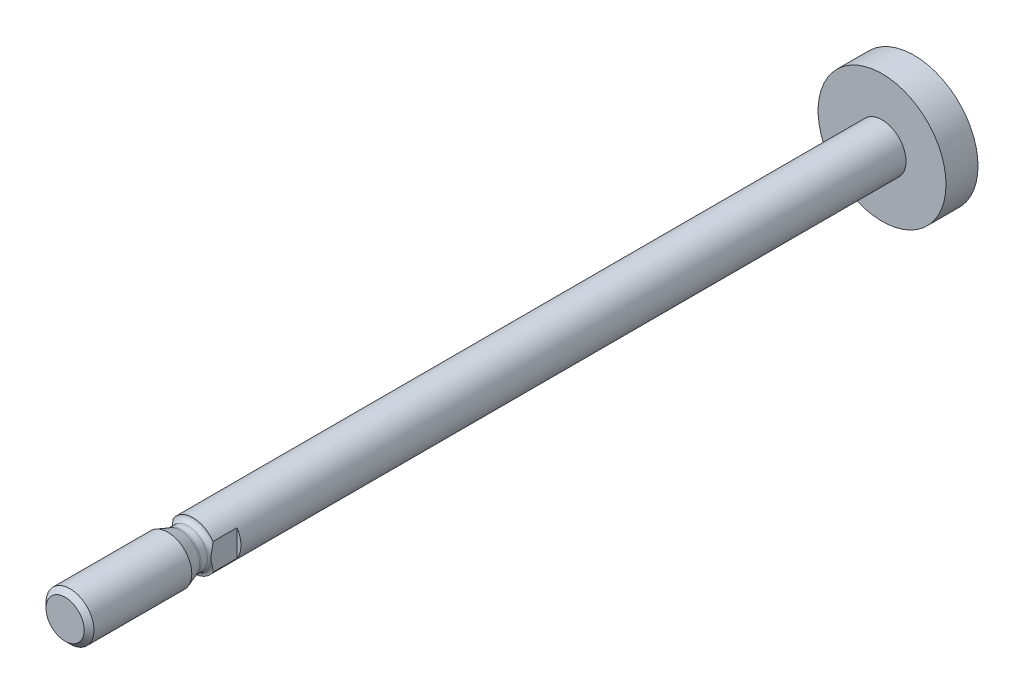
SolidWorks part; units mm, degrees
ref_plane "Front Plane" through (0, 0, 0) normal (0, 0, 1) x (1, 0, 0)
ref_plane "Top Plane" through (0, 0, 0) normal (0, 1, 0) x (1, 0, 0)
ref_plane "Right Plane" through (0, 0, 0) normal (1, 0, 0) x (0, 0, -1)
sketch "Sketch1" plane through (0, 0, 0) normal (1, 0, 0) x (0, 0, -1)
  line L0 (-5, 0) -> (-5, 3)
  line L1 (-5, 3) -> (81.2, 3)
  line L2 (81.2, 3) -> (81.2, 8)
  line L3 (81.2, 8) -> (85.2, 8)
  line L4 (85.2, 8) -> (85.2, 0)
  line L5 (85.2, 0) -> (-5, 0)
  line L6 (85.2, 0) -> (-5, 0) construction
revolve "Revolve1" add sketch "Sketch1" angle 360 about L6 reverse direction yes
sketch "Sketch2" plane through (0, 0, 0) normal (1, 0, 0) x (0, 0, -1)
  line L0 (-21, 0) -> (-21, 2.3865)
  line L1 (-21, 2.3865) -> (-20.3865, 3)
  line L2 (-20.3865, 3) -> (-8.1485, 3)
  line L3 (-8.1485, 3) -> (-6.5994, 2.4362)
  line L4 (-6.3942, 2.4) -> (-5.6, 2.4)
  line L5 (-5, 3) -> (-4, 3)
  line L6 (-4, 3) -> (-4, 0)
  line L7 (-4, 0) -> (-21, 0)
  line L8 (-4, 0) -> (-21, 0) construction
  arc A0 (-6.5994, 2.4362) -> (-6.3942, 2.4) centre (-6.3942, 3) ccw
  arc A1 (-5.6, 2.4) -> (-5, 3) centre (-5.6, 3) ccw
revolve "Revolve2" add sketch "Sketch2" angle 360 about L8 reverse direction yes
cosmetic thread "Cosmetic Thread1" parameters "D1"=12.8515, "D2"=4.773
ref_plane "Plane1" through (0, 0, 5) normal (0, 0, 1) x (1, 0, 0)
ref_plane "Plane2" through (0, 0, 2) normal (0, 0, 1) x (1, 0, 0)
sketch "Sketch3" plane through (0, 0, 2) normal (0, 0, 1) x (1, 0, 0)
  line L0 (-5, 10) -> (-5, -5)
  line L1 (-5, -5) -> (-2.5, -5)
  line L2 (-2.5, -5) -> (-2.5, 5)
  line L3 (-2.5, 5) -> (2.5, 5)
  line L4 (2.5, 5) -> (2.5, -5)
  line L5 (2.5, -5) -> (5, -5)
  line L6 (5, -5) -> (5, 10)
  line L7 (5, 10) -> (-5, 10)
extrude "Cut-Extrude1" cut sketch "Sketch3" along normal blind 4
ref_plane "Plane3" through (0, 0, -175) normal (0, 0, 1) x (1, 0, 0)
ref_plane "Plane4" through (0, 0, 16) normal (0, 0, 1) x (1, 0, 0)
ref_plane "Plane5" through (0, 0, 11.2) normal (0, 0, 1) x (1, 0, 0)
ref_plane "FDT_KSAUFSATZ XY" through (0, 0, 11.2) normal (0, 0, 1) x (1, 0, 0)
ref_plane "FDT_KSAUFSATZ XZ" through (0, 0, 0) normal (0, 1, 0) x (1, 0, 0)
ref_plane "FDT_KSAUFSATZ YZ" through (0, 0, 0) normal (-1, 0, 0) x (0, 0, 1)
ref_axis "FDT_KSAUFSATZ X" through (80.9, 0, 11.2) along (-1, 0, 0)
ref_axis "FDT_KSAUFSATZ Y" through (0, 50, 11.2) along (0, -1, 0)
ref_axis "FDT_KSAUFSATZ Z" through (0, 0, 80.9) along (0, 0, -1)
sketch3d "FDT_KSAUFSATZ"
  point P0 (0, 0, 11.2)
ref_plane "FDT_NUT XY" through (0, 0, 11.2) normal (0, 0, 1) x (1, 0, 0)
ref_plane "FDT_NUT XZ" through (0, 0, 0) normal (0, 1, 0) x (1, 0, 0)
ref_plane "FDT_NUT YZ" through (0, 0, 0) normal (-1, 0, 0) x (0, 0, 1)
ref_axis "FDT_NUT X" through (80.9, 0, 11.2) along (-1, 0, 0)
ref_axis "FDT_NUT Y" through (0, 50, 11.2) along (0, -1, 0)
ref_axis "FDT_NUT Z" through (0, 0, 80.9) along (0, 0, -1)
sketch3d "FDT_NUT"
  point P0 (0, 0, 11.2)
ref_plane "KS XY" through (0, 0, 0) normal (0, 0, -1) x (-1, 0, 0)
ref_plane "KS XZ" through (0, 0, 0) normal (0, 1, 0) x (1, 0, 0)
ref_plane "KS YZ" through (0, 0, 0) normal (1, 0, 0) x (0, 0, -1)
ref_axis "KS X" through (-80.9, 0, 0) along (1, 0, 0)
ref_axis "KS Y" through (0, 50, 0) along (0, -1, 0)
ref_axis "KS Z" through (0, 0, -80.9) along (0, 0, 1)
sketch3d "KS"
  point P0 (0, 0, 0)
ref_plane "NUT1 XY" through (0, 0, 16) normal (0, 0, 1) x (1, 0, 0)
ref_plane "NUT1 XZ" through (0, 0, 0) normal (0, -1, 0) x (-1, 0, 0)
ref_plane "NUT1 YZ" through (0, 0, 0) normal (1, 0, 0) x (0, 0, -1)
ref_axis "NUT1 X" through (-80.9, 0, 16) along (1, 0, 0)
ref_axis "NUT1 Y" through (0, -50, 16) along (0, 1, 0)
ref_axis "NUT1 Z" through (0, 0, 80.9) along (0, 0, -1)
sketch3d "NUT1"
  point P0 (0, 0, 16)
